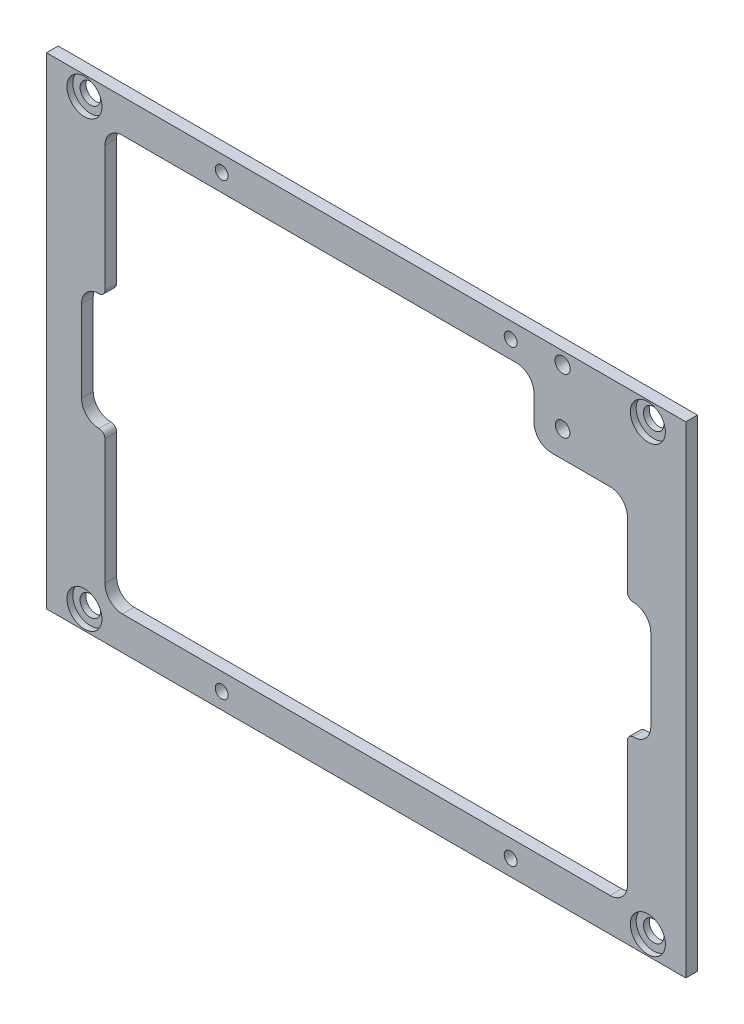
SolidWorks part; units mm, degrees
ref_plane "Front Plane" through (0, 0, 0) normal (0, 0, 1) x (1, 0, 0)
ref_plane "Top Plane" through (0, 0, 0) normal (0, 1, 0) x (1, 0, 0)
ref_plane "Right Plane" through (0, 0, 0) normal (1, 0, 0) x (0, 0, -1)
sketch "Sketch1" plane through (0, 0, 0) normal (0, 0, 1) x (1, 0, 0)
  line L0 (55.75, -83) -> (-55.75, -83) construction
  line L1 (-54.75, -0.5) -> (54.75, -0.5)
  line L2 (-54.75, -0.5) -> (-54.75, -83)
  line L3 (-54.75, -83) -> (54.75, -83)
  line L4 (54.75, -0.5) -> (54.75, -83)
  line L5 (-54.75, -41.75) -> (54.75, -41.75) construction
  line L6 (28.75, -9.25) -> (28.75, -13.6)
  line L7 (-41.75, -6.25) -> (25.75, -6.25)
  line L8 (-44.75, -9.25) -> (-44.75, -31.75)
  line L9 (-41.75, -77.25) -> (41.75, -77.25)
  line L10 (44.75, -19.6) -> (44.75, -31.75)
  line L11 (31.75, -16.6) -> (41.75, -16.6)
  line L12 (54.75, -41.75) -> (48.75, -41.75) construction
  line L13 (48.75, -41.75) -> (48.75, -51.75)
  line L14 (44.75, -31.75) -> (48.75, -31.75)
  line L15 (-44.75, -31.75) -> (-48.75, -31.75)
  line L16 (44.75, -51.75) -> (48.75, -51.75)
  line L17 (48.75, -31.75) -> (48.75, -41.75)
  line L18 (44.75, -51.75) -> (44.75, -74.25)
  line L19 (-48.75, -31.75) -> (-48.75, -51.75)
  line L20 (-48.75, -51.75) -> (-44.75, -51.75)
  line L21 (-44.75, -51.75) -> (-44.75, -74.25)
  arc A0 (41.75, -77.25) -> (44.75, -74.25) centre (41.75, -74.25) ccw
  arc A1 (-44.75, -74.25) -> (-41.75, -77.25) centre (-41.75, -74.25) ccw
  arc A2 (-41.75, -6.25) -> (-44.75, -9.25) centre (-41.75, -9.25) ccw
  arc A3 (28.75, -9.25) -> (25.75, -6.25) centre (25.75, -9.25) ccw
  arc A4 (41.75, -16.6) -> (44.75, -19.6) centre (41.75, -19.6) cw
  arc A5 (28.75, -13.6) -> (31.75, -16.6) centre (31.75, -13.6) ccw
  point P4 (-54.75, -41.75)
  point P24 (28.75, -6.25)
  point P29 (28.75, -16.6)
  dimension "D6" = 3
  dimension "D8" = 3
  dimension "D2" = 109.5
  dimension "D3" = 10
  dimension "D4" = 71
  dimension "D5" = 35.5
  dimension "D7" = 73.5
  dimension "D9" = 16.1
  dimension "D10" = 4
  dimension "D11" = 10
  dimension "D12" = 10
  dimension "D13" = 89.5
  dimension "D14" = 82.5
  dimension "D15" = 10
  dimension "D16" = 10
  dimension "D17" = 4
extrude "Boss-Extrude1" add sketch "Sketch1" along normal blind 2
hole_wizard "Ø3.5 (3.5) Diameter Hole1" positions "Sketch4" profile "Sketch3" hole size "Ø3.5" standard "Ansi Metric" end condition up to next
sketch "Sketch4" plane through (0, 0, 2) normal (0, 0, 1) x (1, 0, 0)
  line L0 (-54.75, -0.5) -> (-54.75, -83) construction
  line L3 (54.75, -83) -> (54.75, -0.5) construction
  line L4 (-54.75, -41.75) -> (54.75, -41.75) construction
  point P0 (-48.25, -3.75)
  point P1 (-48.25, -79.75)
  point P3 (48.25, -79.75)
  point P5 (48.25, -3.75)
  dimension "D1" = 6.5
  dimension "D2" = 38
  dimension "D3" = 6.5
  dimension "D4" = 38
  dimension "D5" = 38
  dimension "D6" = 6.5
  dimension "D7" = 6.5
  dimension "D8" = 38
sketch "Sketch3" plane through (-48.25, -3.75, 2) normal (1, 0, 0) x (0, -1, 0)
  line L0 (0, 0) -> (0, 2)
  line L1 (0, 2) -> (1.75, 2)
  line L2 (1.75, 2) -> (1.75, 0)
  line L5 (1.75, 0) -> (0, 0)
  line L11 (0, -6.35) -> (0, 107.95) construction
  dimension "Thru Hole Dia." = 3.5
  dimension "Thru Hole Depth" = 2
hole_wizard "Ø2.5 (2.5) Diameter Hole1" positions "Sketch6" profile "Sketch5" hole size "Ø2.5" standard "Ansi Metric" end condition up to next
sketch "Sketch6" plane through (0, 0, 2) normal (0, 0, 1) x (1, 0, 0)
  line L1 (41.75, -16.6) -> (31.75, -16.6) construction
  line L2 (54.75, -83) -> (54.75, -0.5) construction
  point P0 (33.65, -12.1)
  dimension "D1" = 21.1
  dimension "D2" = 4.5
sketch "Sketch5" plane through (33.65, -12.1, 2) normal (1, 0, 0) x (0, -1, 0)
  line L0 (0, 0) -> (0, 2)
  line L1 (0, 2) -> (1.25, 2)
  line L2 (1.25, 2) -> (1.25, 0)
  line L5 (1.25, 0) -> (0, 0)
  line L11 (0, -6.35) -> (0, 107.95) construction
  dimension "Thru Hole Dia." = 2.5
  dimension "Thru Hole Depth" = 2
hole_wizard "Ø2.6 (2.6) Diameter Hole1" positions "Sketch8" profile "Sketch7" hole size "Ø2.6" standard "Ansi Metric" end condition up to next
sketch "Sketch8" plane through (0, 0, 2) normal (0, 0, 1) x (1, 0, 0)
  line L1 (54.75, -83) -> (54.75, -0.5) construction
  circle A0 centre (33.65, -12.1) radius 1.35 construction
  point P0 (33.65, -2.57)
  dimension "D2" = 9.53
  dimension "D1" = 21.1
sketch "Sketch7" plane through (33.65, -2.57, 2) normal (1, 0, 0) x (0, -1, 0)
  line L0 (0, 0) -> (0, 2)
  line L1 (0, 2) -> (1.3, 2)
  line L2 (1.3, 2) -> (1.3, 0)
  line L5 (1.3, 0) -> (0, 0)
  line L11 (0, -6.35) -> (0, 107.95) construction
  dimension "Thru Hole Dia." = 2.6
  dimension "Thru Hole Depth" = 2
sketch "Sketch9" plane through (0, 0, 2) normal (0, 0, 1) x (1, 0, 0)
  circle A0 centre (-48.25, -3.75) radius 3
  circle A1 centre (48.25, -3.75) radius 3
  circle A2 centre (48.25, -79.75) radius 3
  circle A3 centre (-48.25, -79.75) radius 3
  dimension "D1" = 6
  dimension "D2" = 6
  dimension "D3" = 6
  dimension "D4" = 6
extrude "Cut-Extrude1" cut sketch "Sketch9" against normal blind 1
hole_wizard "Ø2.2 (2.2) Diameter Hole1" positions "Sketch11" profile "Sketch10" hole size "Ø2.2" standard "Ansi Metric" end condition up to next
sketch "Sketch11" plane through (0, 0, 2) normal (0, 0, 1) x (1, 0, 0)
  line L0 (-54.75, -0.5) -> (-54.75, -83) construction
  line L2 (54.75, -83) -> (54.75, -0.5) construction
  line L4 (-54.75, -41.75) -> (54.75, -41.75) construction
  point P0 (-24.75, -3.25)
  point P1 (24.75, -3.25)
  point P3 (-24.75, -80.25)
  point P5 (24.75, -80.25)
  dimension "D1" = 30
  dimension "D2" = 38.5
  dimension "D3" = 30
  dimension "D4" = 38.5
  dimension "D5" = 38.5
  dimension "D6" = 30
  dimension "D7" = 30
  dimension "D8" = 38.5
sketch "Sketch10" plane through (-24.75, -3.25, 2) normal (1, 0, 0) x (0, -1, 0)
  line L0 (0, 0) -> (0, 2)
  line L1 (0, 2) -> (1.1, 2)
  line L2 (1.1, 2) -> (1.1, 0)
  line L5 (1.1, 0) -> (0, 0)
  line L11 (0, -6.35) -> (0, 107.95) construction
  dimension "Thru Hole Dia." = 2.2
  dimension "Thru Hole Depth" = 2
fillet "Fillet1" radius 1 4 edges at (44.75, -51.75, 1) (44.75, -31.75, 1) (-44.75, -51.75, 1) (-44.75, -31.75, 1)
fillet "Fillet2" radius 3 4 edges at (48.75, -31.75, 1) (48.75, -51.75, 1) (-48.75, -51.75, 1) (-48.75, -31.75, 1)
